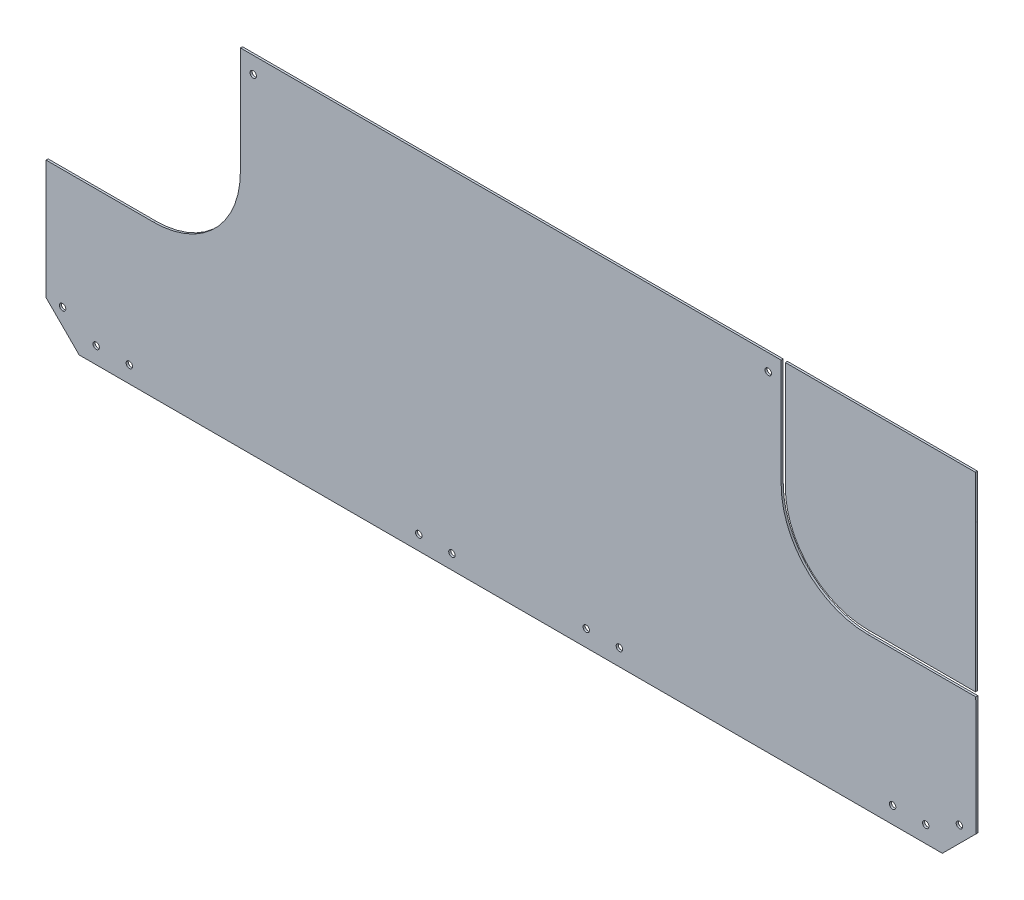
SolidWorks part; units mm, degrees
material "Perspex (TM) GS Acrylic Cast Sheet"
ref_plane "Front Plane" through (0, 0, 0) normal (0, 0, 1) x (1, 0, 0)
ref_plane "Top Plane" through (0, 0, 0) normal (0, 1, 0) x (1, 0, 0)
ref_plane "Right Plane" through (0, 0, 0) normal (1, 0, 0) x (0, 0, -1)
sketch "Sketch1" plane through (0, 0, 0) normal (0, 0, 1) x (1, 0, 0)
  line L1 (-457.2, -304.8) -> (457.2, -304.8)
  line L2 (-457.2, -304.8) -> (-457.2, 304.8)
  line L3 (-457.2, 304.8) -> (457.2, 304.8)
  line L4 (457.2, -304.8) -> (457.2, 304.8)
  line L5 (0, 304.8) -> (0, -304.8) construction
  line L6 (-457.2, 0) -> (457.2, 0) construction
  point P0 (0, 0)
  point P4 (-320.04, 0)
  point P5 (320.04, 0)
  point P6 (0, 213.36)
  point P7 (0, -213.36)
  dimension "Length" = 914.4
  dimension "Width" = 609.6
  dimension "Break" = 137.16
  dimension "D2" = 137.16
  dimension "D1" = 91.44
  dimension "D3" = 91.44
sketch "Sketch2" plane through (0, 0, 0) normal (1, 0, 0) x (0, 0, -1)
  line L0 (-0.7938, -304.8) -> (0.7938, -304.8)
  dimension "Thickness" = 1.5875
sketch "Sketch3" plane through (0, 0, 0) normal (0, 0, 1) x (1, 0, 0)
  line L0 (-457.2, -304.8) -> (-457.2, 304.8) construction
  line L1 (-457.2, -304.8) -> (457.2, -304.8) construction
  line L2 (457.2, -304.8) -> (457.2, 304.8) construction
  line L3 (-457.2, 304.8) -> (457.2, 304.8) construction
  line L4 (-457.2, -304.8) -> (-457.2, 304.8)
  line L5 (-457.2, -304.8) -> (457.2, -304.8)
  line L6 (457.2, -304.8) -> (457.2, 304.8)
  line L7 (-457.2, 304.8) -> (457.2, 304.8)
extrude "Boss-Extrude1" add sketch "Sketch3" along normal mid plane 1.5875
sketch "Sketch4" plane through (0, 0, 0.7937) normal (0, 0, 1) x (1, 0, 0)
  line L0 (-378.2467, -279.4) -> (-378.2467, -39.3705)
  line L1 (-457.2, -304.8) -> (457.2, -304.8) construction
  line L2 (-378.2467, -751.2581) -> (-378.2467, -65.4581) construction
  line L3 (-378.2467, -39.3705) -> (333.614, -39.3705)
  line L4 (333.614, -39.3705) -> (333.9807, -279.0843)
  line L5 (334.0201, -317.5147) -> (334.0201, -266.7147) construction
  line L6 (334.0201, -304.8) -> (457.2, -304.8)
  line L7 (457.2, -304.8) -> (457.2, 304.8)
  line L8 (457.2, 304.8) -> (-457.2, 304.8)
  line L9 (-457.2, 304.8) -> (-457.2, -304.8)
  line L10 (-457.2, -304.8) -> (-378.2467, -304.8)
  line L11 (-378.2467, -304.8) -> (-352.8467, -304.8)
  line L12 (-352.8467, -751.2581) -> (-352.8467, -65.4581) construction
  line L13 (-352.8467, -304.8) -> (-378.2467, -279.4)
  line L14 (334.0201, -304.8) -> (308.2651, -304.8)
  line L15 (308.2651, -39.3463) -> (308.2651, -725.1463) construction
  line L16 (308.2651, -304.8) -> (333.9807, -279.0843)
extrude "Cut-Extrude1" cut sketch "Sketch4" against normal blind 2.54
sketch "Sketch7" plane through (0, 0, 0.7937) normal (0, 0, 1) x (1, 0, 0)
  line L0 (-378.2467, -188.1903) -> (-378.2467, -39.3463)
  line L3 (-378.2467, -39.3463) -> (-229.4027, -39.3463)
  line L10 (-229.4027, -64.7463) -> (-229.4027, -39.3463)
  line L11 (-229.4027, -64.7463) -> (-229.4027, -121.8963)
  line L12 (-352.8467, -188.1903) -> (-295.6967, -188.1903)
  line L13 (-352.8467, -188.1903) -> (-378.2467, -188.1903)
  arc A1 (-229.4027, -121.8963) -> (-295.6967, -188.1903) centre (-295.6967, -121.8963) cw
extrude "Cut-Extrude2" cut sketch "Sketch7" against normal blind 2.54
sketch "Sketch8" plane through (0, 0, 0.7937) normal (0, 0, 1) x (1, 0, 0)
  line L0 (251.1151, -185.0153) -> (333.6651, -185.0153)
  line L1 (333.6651, -39.3463) -> (333.6651, -725.1463) construction
  line L2 (333.6651, -185.0153) -> (333.6651, -39.3463)
  line L3 (187.9961, -121.8963) -> (187.9961, -39.3463)
  line L4 (-378.2467, -39.3463) -> (307.5533, -39.3463) construction
  line L5 (187.9961, -39.3463) -> (333.6651, -39.3463)
  line L6 (251.1151, -188.1903) -> (336.8401, -188.1903)
  line L7 (336.8401, -188.1903) -> (336.8401, -36.1713)
  line L8 (184.8211, -36.1713) -> (336.8401, -36.1713)
  line L9 (184.8211, -121.8963) -> (184.8211, -36.1713)
  arc A0 (187.9961, -121.8963) -> (251.1151, -185.0153) centre (251.1151, -121.8963) ccw
  arc A1 (184.8211, -121.8963) -> (251.1151, -188.1903) centre (251.1151, -121.8963) ccw
  dimension "D1" = 3.175
extrude "Cut-Extrude3" cut sketch "Sketch8" against normal blind 2.54
sketch "Sketch9" plane through (0, 0, 0.7937) normal (0, 0, 1) x (1, 0, 0)
  point P0 (-365.5467, -279.4147)
  point P1 (-339.7911, -292.1147)
  point P3 (-314.3911, -292.1147)
  point P5 (-365.5467, -229.8463)
  point P7 (-92.7507, -293.7022)
  point P9 (-67.3507, -293.7022)
  point P11 (35.5193, -292.1147)
  point P13 (60.9193, -292.1147)
  point P15 (270.1645, -292.1147)
  point P17 (295.5645, -292.1147)
  point P19 (321.3201, -279.4147)
  point P21 (320.9651, -229.8463)
  point P23 (-219.4967, -52.0463)
  point P25 (174.9151, -52.0463)
hole_wizard "#10 (0.1935) Diameter Hole1" positions "Sketch10" profile "Sketch11" hole size "#10" standard "ANSI Inch" end condition through all
sketch "Sketch10" plane through (0, 0, 0.7937) normal (0, 0, 1) x (1, 0, 0)
  point P0 (-314.3911, -292.1147)
  point P3 (-339.7911, -292.1147)
  point P6 (-365.5467, -279.4147)
  point P9 (-92.7507, -293.7022)
  point P12 (-67.3507, -293.7022)
  point P15 (35.5193, -292.1147)
  point P18 (60.9193, -292.1147)
  point P21 (295.5645, -292.1147)
  point P24 (270.1645, -292.1147)
  point P27 (321.3201, -279.4147)
  point P31 (174.9151, -52.0463)
  point P34 (-219.4967, -52.0463)
sketch "Sketch11" plane through (-314.3911, -292.1147, 0.7937) normal (1, 0, 0) x (0, -1, 0)
  line L0 (0, 0) -> (0, 1.5875)
  line L1 (0, 1.5875) -> (2.4574, 1.5875)
  line L2 (2.4574, 1.5875) -> (2.4574, 0)
  line L5 (2.4574, 0) -> (0, 0)
  line L11 (0, -6.35) -> (0, 107.95) construction
  dimension "Thru Hole Dia." = 4.9149
  dimension "Thru Hole Depth" = 1.5875
equation "\"D1@Boss-Extrude1\"=\"thickness@sketch2\""
equation "\"Break@Sketch1\" = \"Length@Sketch1\" * 0.15"
equation "\"D2@Sketch1\" = \"Break@Sketch1\""
equation "\"D1@Sketch1\"=\"Width@Sketch1\"*0.15"
equation "\"D3@Sketch1\"=\"D1@Sketch1\""
